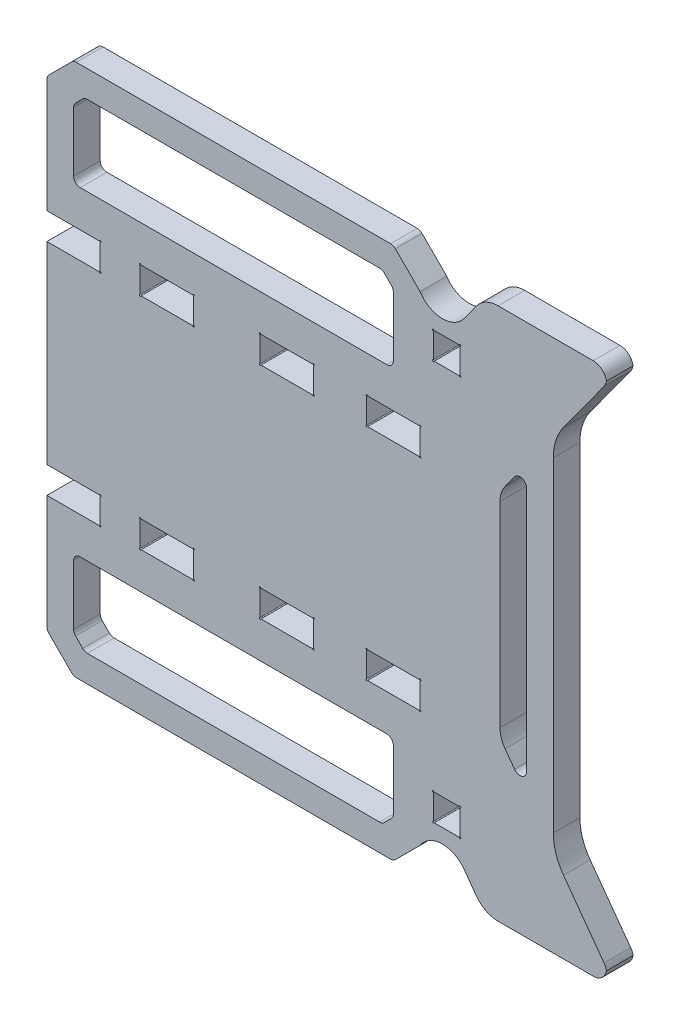
SolidWorks part; units mm, degrees
ref_plane "Front Plane" through (0, 0, 0) normal (0, 0, 1) x (1, 0, 0)
ref_plane "Top Plane" through (0, 0, 0) normal (0, 1, 0) x (1, 0, 0)
ref_plane "Right Plane" through (0, 0, 0) normal (1, 0, 0) x (0, 0, -1)
sketch "Sketch1" plane through (0, 0, 0) normal (0, 0, 1) x (1, 0, 0)
  line L0 (83.672, 0) -> (-43.8164, 0) construction
  line L1 (10.525, 38.1) -> (10.525, -38.1) construction
  line L2 (-27.575, 38.1) -> (48.625, 38.1)
  line L3 (99.425, -63.5) -> (99.425, -60.325)
  line L4 (99.425, -60.325) -> (74.025, -25.4)
  line L5 (-27.575, -63.5) -> (48.625, -63.5)
  line L6 (-27.575, 38.1) -> (-27.575, 54.5197)
  line L7 (48.625, 38.1) -> (48.625, 54.5197)
  line L8 (-24.9447, 57.15) -> (45.9947, 57.15)
  line L9 (-27.575, 63.5) -> (48.625, 63.5)
  line L10 (-33.925, 57.15) -> (-33.925, -57.15)
  line L11 (-27.575, 63.5) -> (-33.925, 57.15)
  line L12 (-24.9447, 57.15) -> (-27.575, 54.5197)
  line L13 (99.425, 63.5) -> (99.425, 60.325)
  line L14 (-23.0849, 59.0099) -> (-29.4349, 52.6599) construction
  line L15 (99.425, 60.325) -> (74.025, 25.4)
  line L16 (74.025, 25.4) -> (74.025, -25.4)
  line L17 (48.625, -38.1) -> (48.625, -54.5197)
  line L18 (-27.575, -38.1) -> (48.625, -38.1)
  line L19 (-24.9447, -57.15) -> (45.9947, -57.15)
  line L20 (-24.9447, -57.15) -> (-27.575, -54.5197)
  line L21 (-27.575, -38.1) -> (-27.575, -54.5197)
  line L22 (-27.575, -63.5) -> (-33.925, -57.15)
  line L23 (48.625, -63.5) -> (54.975, -57.15)
  line L24 (48.625, 63.5) -> (54.975, 57.15)
  line L25 (70.3271, -63.5) -> (99.425, -63.5)
  line L26 (45.9947, 57.15) -> (48.625, 54.5197)
  line L27 (45.9947, -57.15) -> (48.625, -54.5197)
  line L28 (70.3271, 63.5) -> (65.7089, 57.15)
  line L29 (70.3271, 63.5) -> (99.425, 63.5)
  line L30 (78.8831, 75.2646) -> (53.4831, 40.3396) construction
  line L31 (54.975, -42.3909) -> (54.975, -57.15)
  line L32 (70.3271, -63.5) -> (65.7089, -57.15)
  line L34 (48.625, -63.5) -> (54.975, -57.15)
  line L35 (65.7089, 57.15) -> (54.975, 42.3909)
  line L36 (54.975, 42.3909) -> (54.975, 57.15)
  line L37 (65.7089, -57.15) -> (54.975, -42.3909)
  point P7 (-27.575, 0)
  point P21 (74.025, 0)
  point P22 (-33.925, 0)
  dimension "D1" = 25.4
  dimension "D2" = 76.2
  dimension "D3" = 127
  dimension "D4" = 6.35
  dimension "D7" = 3.175
  dimension "D8" = 25.4
  dimension "D9" = 25.4
  dimension "D6" = 6.35
extrude "Boss-Extrude1" add sketch "Sketch1" along normal blind 6.35 contours L23 L32 L25 L3 L4 L16 L15 L13 L29 L28 L24 L9 L11 L10 L22 L5 L8 L26 L7 L2 L6 L12 L27 L19 L20 L21 L18 L17 region at (27.1557, 0, 0)
fillet "Fillet1" radius 6.35 4 edges at (70.3271, 63.5, 3.175) (70.3271, -63.5, 3.175) (54.975, -42.3909, 3.175) (54.975, 42.3909, 3.175)
fillet "Fillet3" radius 3.175 4 edges at (99.425, 63.5, 3.175) (99.425, 60.325, 3.175) (99.425, -60.325, 3.175) (99.425, -63.5, 3.175)
fillet "Fillet4" radius 6.35 2 edges at (74.025, -25.4, 3.175) (74.025, 25.4, 3.175)
fillet "Fillet7" radius 1.5875 4 edges at (-27.575, -38.1, 3.175) (48.625, -38.1, 3.175) (48.625, 38.1, 3.175) (-27.575, 38.1, 3.175)
fillet "Fillet8" radius 1.5875 6 edges at (-33.925, -57.15, 3.175) (-27.575, -63.5, 3.175) (48.625, -63.5, 3.175) (48.625, 63.5, 3.175) (-27.575, 63.5, 3.175) (-33.925, 57.15, 3.175)
fillet "Fillet9" radius 1.5875 8 edges at (-27.575, 54.5197, 3.175) (-24.9447, 57.15, 3.175) (-27.575, -54.5197, 3.175) (-24.9447, -57.15, 3.175) (45.9947, -57.15, 3.175) (48.625, -54.5197, 3.175) (48.625, 54.5197, 3.175) (45.9947, 57.15, 3.175)
sketch "Sketch2" plane through (0, 0, 6.35) normal (0, 0, 1) x (1, 0, 0)
  line L0 (-33.925, 0) -> (74.025, 0) construction
  line L1 (-33.925, 56.4924) -> (-33.925, -56.4924) construction
  line L2 (74.025, 23.3351) -> (74.025, -23.3351) construction
  line L3 (48.625, 39.6875) -> (48.625, 53.8622) construction
  line L4 (58.3484, 50.8) -> (64.3016, 50.8)
  line L5 (58.15, 50.6016) -> (58.15, 44.6484)
  line L6 (58.3484, 44.45) -> (64.3016, 44.45)
  line L7 (64.5, 50.6016) -> (64.5, 44.6484)
  line L8 (64.5, -50.6016) -> (64.5, -44.6484)
  line L9 (58.3484, -50.8) -> (64.3016, -50.8)
  line L10 (58.15, -50.6016) -> (58.15, -44.6484)
  line L11 (58.3484, -44.45) -> (64.3016, -44.45)
  arc A0 (58.3484, 50.8) -> (58.15, 50.6016) centre (58.15, 50.8) ccw
  arc A1 (64.5, 50.6016) -> (64.3016, 50.8) centre (64.5, 50.8) ccw
  arc A2 (64.3016, 44.45) -> (64.5, 44.6484) centre (64.5, 44.45) ccw
  arc A3 (58.15, 44.6484) -> (58.3484, 44.45) centre (58.15, 44.45) ccw
  arc A4 (64.3016, -44.45) -> (64.5, -44.6484) centre (64.5, -44.45) cw
  arc A5 (64.5, -50.6016) -> (64.3016, -50.8) centre (64.5, -50.8) cw
  arc A6 (58.3484, -50.8) -> (58.15, -50.6016) centre (58.15, -50.8) cw
  arc A7 (58.15, -44.6484) -> (58.3484, -44.45) centre (58.15, -44.45) cw
  point P10 (48.625, 46.7748)
  dimension "D5" = 0.3969
  dimension "D6" = 0.3969
  dimension "D7" = 0.3969
  dimension "D8" = 0.3969
  dimension "D1" = 6.35
  dimension "D2" = 6.35
  dimension "D3" = 50.8
  dimension "D4" = 9.525
extrude "Cut-Extrude1" cut sketch "Sketch2" against normal through all
sketch "Sketch5" plane through (0, 0, 6.35) normal (0, 0, 1) x (1, 0, 0)
  line L0 (-33.925, 29.3675) -> (74.025, 29.3675) construction
  line L1 (-33.925, 56.4924) -> (-33.925, -56.4924) construction
  line L2 (74.025, 23.3351) -> (74.025, -23.3351) construction
  line L3 (-25.9875, 38.1) -> (47.0375, 38.1) construction
  line L4 (-33.925, 23.0175) -> (74.025, 23.0175) construction
  line L5 (-33.925, 0) -> (74.025, 0) construction
  line L6 (-11.5016, 29.3675) -> (0.8016, 29.3675)
  line L7 (-11.7, 29.169) -> (-11.7, 23.2159)
  line L8 (-11.5016, 23.0175) -> (0.8016, 23.0175)
  line L9 (1, 29.169) -> (1, 23.2159)
  line L10 (42.4734, 29.3675) -> (54.7766, 29.3675)
  line L11 (42.275, 29.169) -> (42.275, 23.2159)
  line L12 (42.4734, 23.0175) -> (54.7766, 23.0175)
  line L13 (54.975, 29.169) -> (54.975, 23.2159)
  line L14 (29.3766, 29.3675) -> (17.0734, 29.3675)
  line L15 (29.575, 29.169) -> (29.575, 23.2159)
  line L16 (29.3766, 23.0175) -> (17.0734, 23.0175)
  line L17 (16.875, 29.169) -> (16.875, 23.2159)
  line L18 (-21.4234, 29.3675) -> (-33.925, 29.3675)
  line L19 (-21.225, 29.169) -> (-21.225, 23.2159)
  line L20 (-21.4234, 23.0175) -> (-33.925, 23.0175)
  line L21 (-33.925, 29.3675) -> (-33.925, 23.0175)
  line L22 (-33.925, -29.3675) -> (-33.925, -23.0175)
  line L23 (-21.4234, -23.0175) -> (-33.925, -23.0175)
  line L24 (-21.225, -29.169) -> (-21.225, -23.2159)
  line L25 (-21.4234, -29.3675) -> (-33.925, -29.3675)
  line L26 (16.875, -29.169) -> (16.875, -23.2159)
  line L27 (29.3766, -23.0175) -> (17.0734, -23.0175)
  line L28 (29.575, -29.169) -> (29.575, -23.2159)
  line L29 (29.3766, -29.3675) -> (17.0734, -29.3675)
  line L30 (54.975, -29.169) -> (54.975, -23.2159)
  line L31 (42.4734, -23.0175) -> (54.7766, -23.0175)
  line L32 (42.275, -29.169) -> (42.275, -23.2159)
  line L33 (42.4734, -29.3675) -> (54.7766, -29.3675)
  line L34 (1, -29.169) -> (1, -23.2159)
  line L35 (-11.5016, -23.0175) -> (0.8016, -23.0175)
  line L36 (-11.7, -29.169) -> (-11.7, -23.2159)
  line L37 (-11.5016, -29.3675) -> (0.8016, -29.3675)
  line L38 (-33.925, 26.1925) -> (54.975, 26.1925) construction
  arc A0 (-21.225, 29.169) -> (-21.4234, 29.3675) centre (-21.225, 29.3675) ccw
  arc A1 (-11.5016, 29.3675) -> (-11.7, 29.169) centre (-11.7, 29.3675) ccw
  arc A2 (1, 29.169) -> (0.8016, 29.3675) centre (1, 29.3675) ccw
  arc A3 (29.575, 29.169) -> (29.3766, 29.3675) centre (29.575, 29.3675) ccw
  arc A4 (17.0734, 29.3675) -> (16.875, 29.169) centre (16.875, 29.3675) ccw
  arc A5 (54.975, 29.169) -> (54.7766, 29.3675) centre (54.975, 29.3675) ccw
  arc A6 (42.4734, 29.3675) -> (42.275, 29.169) centre (42.275, 29.3675) ccw
  arc A7 (17.0734, 23.0175) -> (16.875, 23.2159) centre (16.875, 23.0175) cw
  arc A8 (29.575, 23.2159) -> (29.3766, 23.0175) centre (29.575, 23.0175) cw
  arc A9 (42.4734, 23.0175) -> (42.275, 23.2159) centre (42.275, 23.0175) cw
  arc A10 (54.975, 23.2159) -> (54.7766, 23.0175) centre (54.975, 23.0175) cw
  arc A11 (1, 23.2159) -> (0.8016, 23.0175) centre (1, 23.0175) cw
  arc A12 (-11.5016, 23.0175) -> (-11.7, 23.2159) centre (-11.7, 23.0175) cw
  arc A13 (-21.225, 23.2159) -> (-21.4234, 23.0175) centre (-21.225, 23.0175) cw
  arc A14 (-21.225, -23.2159) -> (-21.4234, -23.0175) centre (-21.225, -23.0175) ccw
  arc A15 (-11.5016, -23.0175) -> (-11.7, -23.2159) centre (-11.7, -23.0175) ccw
  arc A16 (1, -23.2159) -> (0.8016, -23.0175) centre (1, -23.0175) ccw
  arc A17 (54.975, -23.2159) -> (54.7766, -23.0175) centre (54.975, -23.0175) ccw
  arc A18 (42.4734, -23.0175) -> (42.275, -23.2159) centre (42.275, -23.0175) ccw
  arc A19 (29.575, -23.2159) -> (29.3766, -23.0175) centre (29.575, -23.0175) ccw
  arc A20 (17.0734, -23.0175) -> (16.875, -23.2159) centre (16.875, -23.0175) ccw
  arc A21 (42.4734, -29.3675) -> (42.275, -29.169) centre (42.275, -29.3675) cw
  arc A22 (54.975, -29.169) -> (54.7766, -29.3675) centre (54.975, -29.3675) cw
  arc A23 (17.0734, -29.3675) -> (16.875, -29.169) centre (16.875, -29.3675) cw
  arc A24 (29.575, -29.169) -> (29.3766, -29.3675) centre (29.575, -29.3675) cw
  arc A25 (1, -29.169) -> (0.8016, -29.3675) centre (1, -29.3675) cw
  arc A26 (-11.5016, -29.3675) -> (-11.7, -29.169) centre (-11.7, -29.3675) cw
  arc A27 (-21.225, -29.169) -> (-21.4234, -29.3675) centre (-21.225, -29.3675) cw
  dimension "D11" = 0.3969
  dimension "D12" = 0.3969
  dimension "D13" = 0.3969
  dimension "D14" = 0.3969
  dimension "D15" = 0.3969
  dimension "D16" = 0.3969
  dimension "D17" = 0.3969
  dimension "D1" = 8.7325
  dimension "D3" = 12.7
  dimension "D4" = 12.7
  dimension "D5" = 41.275
  dimension "D6" = 34.925
  dimension "D7" = 12.7
  dimension "D8" = 12.7
  dimension "D9" = 50.8
  dimension "D10" = 0
  dimension "D2" = 6.35
extrude "Cut-Extrude4" cut sketch "Sketch5" against normal through all
sketch "Sketch6" plane through (0, 0, 6.35) normal (0, 0, 1) x (1, 0, 0)
  line L0 (80.375, 34.1312) -> (80.375, -34.1312)
  line L1 (98.8177, 59.49) -> (75.2395, 27.07) construction
  line L2 (98.8177, -59.49) -> (75.2395, -27.07) construction
  line L3 (74.025, 23.3351) -> (74.025, -23.3351) construction
  line L4 (86.725, 34.1312) -> (86.725, -34.1312)
  line L5 (86.725, 34.1312) -> (86.725, 42.8625)
  line L6 (86.725, 42.8625) -> (80.375, 34.1312)
  line L7 (86.725, -34.1312) -> (86.725, -42.8625)
  line L8 (86.725, -42.8625) -> (80.375, -34.1312)
  dimension "D1" = 6.35
  dimension "D2" = 6.35
extrude "Boss-Extrude2" add sketch "Sketch6" against normal blind 6.35
fillet "Fillet10" radius 1.5875 2 edges at (80.375, -34.1312, 3.175) (80.375, 34.1312, 3.175)
fillet "Fillet11" radius 12.7 2 edges at (86.725, 42.8625, 3.175) (86.725, -42.8625, 3.175)
